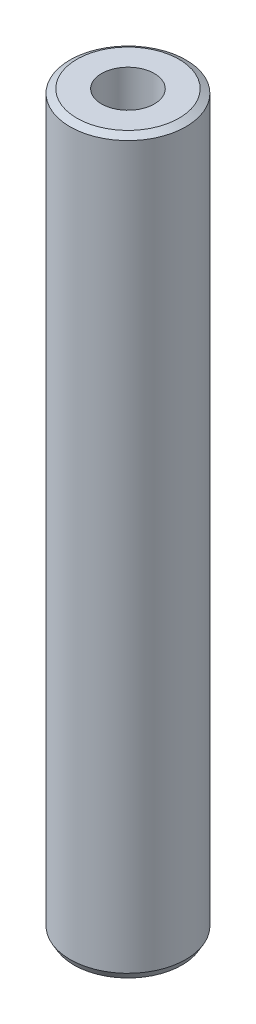
SolidWorks part; units mm, degrees
ref_plane "Front Plane" through (0, 0, 0) normal (0, 0, 1) x (1, 0, 0)
ref_plane "Top Plane" through (0, 0, 0) normal (0, 1, 0) x (1, 0, 0)
ref_plane "Right Plane" through (0, 0, 0) normal (1, 0, 0) x (0, 0, -1)
sketch "Sketch1" plane through (0, 0, 0) normal (0, 1, 0) x (1, 0, 0)
  circle A0 centre (0, 0) radius 47.5
  dimension "SHAFT_OD" = 95
extrude "Boss-Extrude1" add sketch "Sketch1" along normal blind 600
sketch "Sketch2" plane through (0, 0, 0) normal (0, 1, 0) x (1, 0, 0)
  circle A0 centre (0, 0) radius 21.6403
  dimension "BORE_D" = 43.2805
extrude "Cut-Extrude1" cut sketch "Sketch2" along normal through all
chamfer "Chamfer1" distance 3.2557 angle 60 2 edges at (0, 600, 47.5) (0, 0, 47.5) first distance on face at (0, 600, 47.5) first distance on face at (0, 0, 21.6403)
